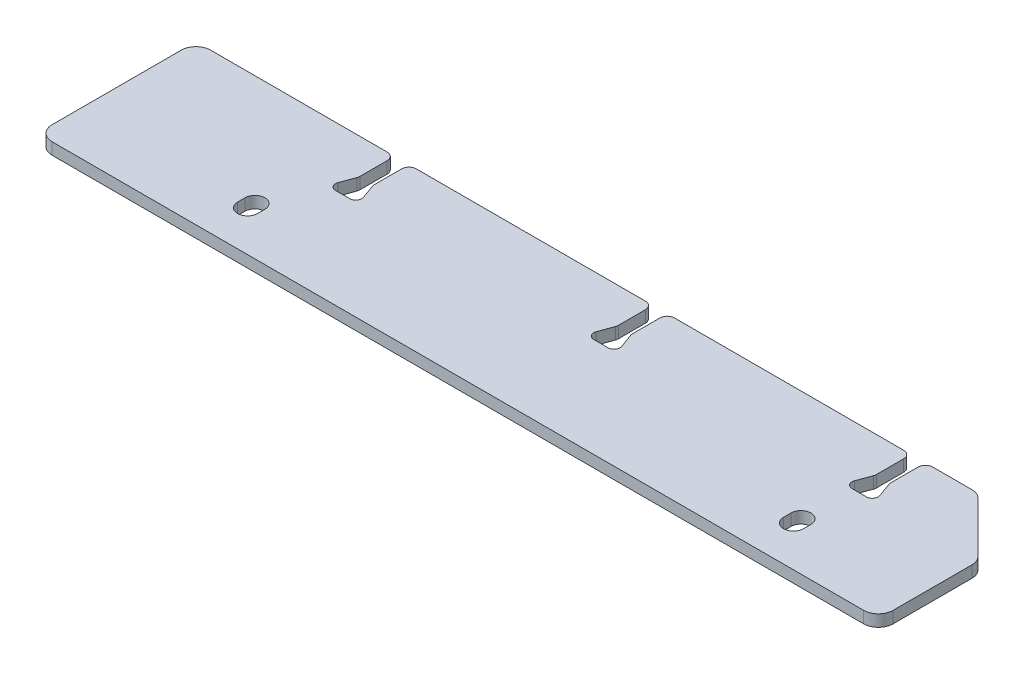
SolidWorks part; units mm, degrees
material "PA Type 6"
ref_plane "Front Plane" through (0, 0, 0) normal (0, 0, 1) x (1, 0, 0)
ref_plane "Top Plane" through (0, 0, 0) normal (0, 1, 0) x (1, 0, 0)
ref_plane "Right Plane" through (0, 0, 0) normal (1, 0, 0) x (0, 0, -1)
ref_axis "Axis1" through (0, 0, 0) along (0, 1, 0)
sketch "Sketch2" plane through (0, 0, 0) normal (0, 1, 0) x (1, 0, 0)
  line L0 (0, 0) -> (0, 21.5) construction
  line L1 (-37, 5.5) -> (-37, 6.5) construction
  line L2 (-60, 0) -> (-60, 21.5)
  line L3 (-60, 21.5) -> (54, 21.5)
  line L4 (54, 0) -> (54, 21.5)
  line L5 (-38.35, 5.5) -> (-38.35, 6.5)
  line L6 (-60, 0) -> (54, 0)
  line L7 (-35.65, 5.5) -> (-35.65, 6.5)
  line L9 (37, 5.5) -> (37, 6.5) construction
  line L10 (35.65, 5.5) -> (35.65, 6.5)
  line L11 (38.35, 5.5) -> (38.35, 6.5)
  circle A0 centre (37, 6) radius 1.35 construction
  arc A1 (-38.35, 5.5) -> (-35.65, 5.5) centre (-37, 5.5) ccw
  arc A2 (-35.65, 6.5) -> (-38.35, 6.5) centre (-37, 6.5) ccw
  arc A3 (35.65, 5.5) -> (38.35, 5.5) centre (37, 5.5) ccw
  circle A4 centre (-37, 6) radius 1.35 construction
  arc A5 (38.35, 6.5) -> (35.65, 6.5) centre (37, 6.5) ccw
  point P10 (-37, 6)
  point P17 (37, 6)
  dimension "D6" = 2.7
  dimension "D1" = 74
  dimension "D2" = 1
  dimension "D3" = 21.5
  dimension "D4" = 6
  dimension "D5" = 60
  dimension "D7" = 54
extrude "Boss-Extrude1" add sketch "Sketch2" along normal blind 1.5875
chamfer "Chamfer1" distance 8 angle 45 1 edges at (54, 0.7937, -21.5)
fillet "Fillet1" radius 2 5 edges at (-60, 0.7937, -21.5) (-60, 0.7937, 0) (54, 0.7937, 0) (54, 0.7937, -13.5) (46, 0.7937, -21.5)
sketch "Sketch3" plane through (0, 0, 0) normal (0, 1, 0) x (1, 0, 0)
  line L0 (-60, 21.5) -> (54, 21.5) construction
  line L1 (-33.075, 21.5) -> (-31.125, 21.5)
  line L2 (-33.075, 21.5) -> (-33.075, 16.639)
  line L3 (-33.075, 13.5) -> (-31.125, 13.5)
  line L4 (-31.125, 21.5) -> (-31.125, 16.639)
  line L5 (-32.1, 13.5) -> (-32.1, 21.5) construction
  line L6 (-33.8268, 14.5736) -> (-33.075, 16.639)
  line L7 (-30.3732, 14.5736) -> (-31.125, 16.639)
  line L8 (-33.075, 16.639) -> (-33.075, 13.5) construction
  arc A0 (-31.125, 13.5) -> (-30.3732, 14.5736) centre (-31.125, 14.3) ccw
  arc A1 (-33.8268, 14.5736) -> (-33.075, 13.5) centre (-33.075, 14.3) ccw
  point P11 (-32.1, 13.5)
  dimension "D1" = 0.8
  dimension "D2" = 1.95
  dimension "D3" = 8
  dimension "D4" = 32.1
  dimension "D5" = 20
extrude "Cut-Extrude1" cut sketch "Sketch3" along normal through all
pattern_linear "LPattern1" count 3 spacing 35 along (1, 0, 0) of "Cut-Extrude1"
fillet "Fillet2" radius 1 6 edges at (38.875, 0.7937, -21.5) (1.925, 0.7937, -21.5) (3.875, 0.7937, -21.5) (-31.125, 0.7937, -21.5) (36.925, 0.7937, -21.5) (-33.075, 0.7937, -21.5)
fillet "Fillet3" radius 1 6 edges at (36.925, 0.7937, -16.639) (38.875, 0.7937, -16.639) (1.925, 0.7937, -16.639) (3.875, 0.7937, -16.639) (-31.125, 0.7937, -16.639) (-33.075, 0.7937, -16.639)
sketch "Sketch4" [suppressed] plane through (0, 0, 0) normal (0, 1, 0) x (1, 0, 0)
  line L0 (-34.075, 21.5) -> (-58, 21.5) construction
  line L1 (-70, 31.5) -> (539.6, 31.5)
  line L2 (-70, 31.5) -> (-70, -273.3)
  line L3 (-70, -273.3) -> (539.6, -273.3)
  line L4 (539.6, 31.5) -> (539.6, -273.3)
  line L5 (-60, 19.5) -> (-60, 2) construction
  line L6 (234.8, 31.5) -> (234.8, -273.3)
  dimension "D1" = 609.6
  dimension "D2" = 304.8
  dimension "D3" = 10
  dimension "D4" = 10
pattern_linear "LPattern2" [suppressed] count 4 spacing 120 count 10 spacing 28.2 of bodies 103
